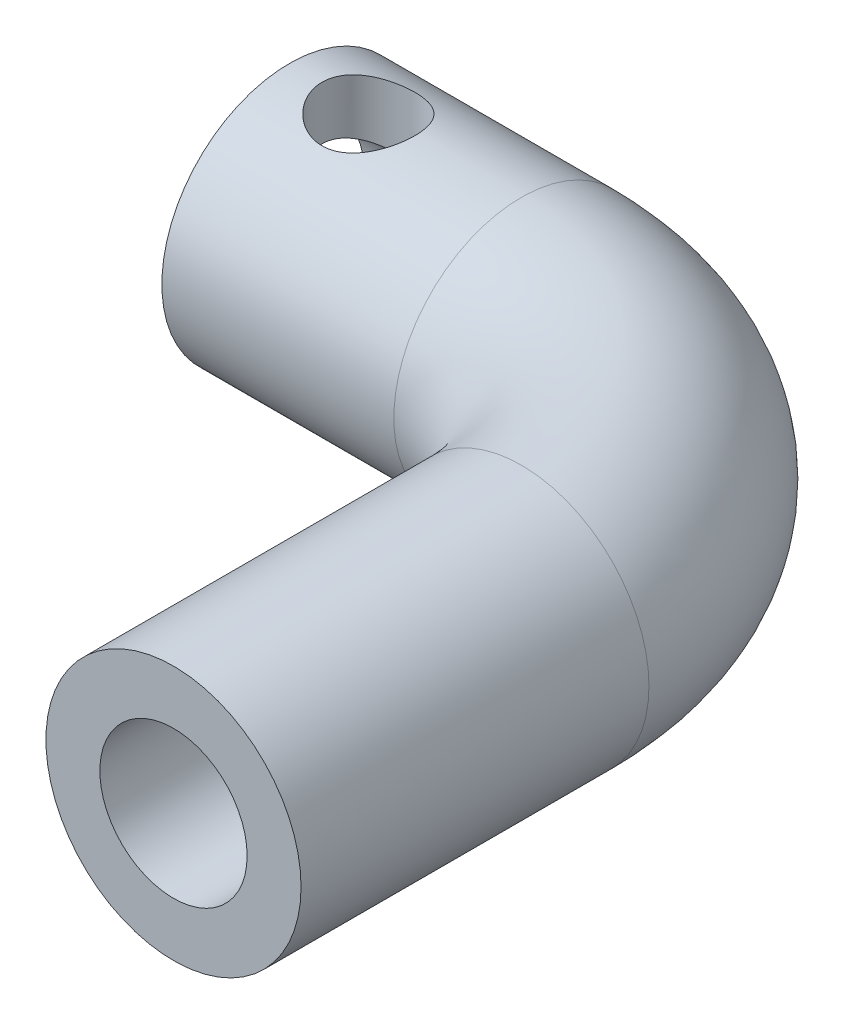
SolidWorks part; units mm, degrees
ref_plane "Front Plane" through (0, 0, 0) normal (0, 0, 1) x (1, 0, 0)
ref_plane "Top Plane" through (0, 0, 0) normal (0, 1, 0) x (1, 0, 0)
ref_plane "Right Plane" through (0, 0, 0) normal (1, 0, 0) x (0, 0, -1)
sketch "PROFILE" plane through (0, 0, 0) normal (0, 1, 0) x (1, 0, 0)
  line L0 (2.5, -10) -> (2.5, -25)
  line L1 (-7.5, 0) -> (-17.5, 0)
  arc A0 (2.5, -10) -> (-7.5, 0) centre (-7.5, -10) ccw
  dimension "D1" = 10
  dimension "D2" = 10
  dimension "D3" = 15
ref_plane "Plane1" through (0, 0, 25) normal (0, 0, 1) x (1, 0, 0)
sketch "Sketch4" plane through (0, 0, 25) normal (0, 0, 1) x (1, 0, 0)
  line L0 (2.5, 0) -> (-7.5, 0) construction
  circle A0 centre (2.5, 0) radius 5.5
  dimension "D1" = 11
sweep "Sweep2" add profiles "Sketch4" path "PROFILE"
sketch "Sketch6" plane through (0, 0, 25) normal (0, 0, 1) x (1, 0, 0)
  circle A0 centre (2.5, 0) radius 3.175
extrude "HOLE_SHAFT" cut sketch "Sketch6" against normal blind 10
sketch "Sketch7" plane through (-17.5, 0, 0) normal (-1, 0, 0) x (0, 0, 1)
  circle A0 centre (0, 0) radius 3.2
extrude "HOLE_POT" cut sketch "Sketch7" against normal blind 10
sketch "Sketch8" plane through (0, 0, 0) normal (0, 1, 0) x (1, 0, 0)
  line L0 (-7.5, 0) -> (-17.5, 0) construction
  circle A0 centre (-14.0963, 0) radius 2
  point P4 (-14.0963, 0)
extrude "Cut-Extrude3" cut sketch "Sketch8" along normal through all
ref_axis "Axis1" through (-18.775, 0, 0) along (1, 0, 0)
ref_plane "Plane2" through (0, 0, 0) normal (0, 1, 0) x (1, 0, 0)
sketch "Sketch11" plane through (-7.5, 0, 0) normal (-1, 0, 0) x (0, 0, 1)
  line L1 (-3.369, 0.5) -> (3.369, 0.5)
  line L2 (-3.369, 0.5) -> (-3.369, -0.5)
  line L3 (-3.369, -0.5) -> (3.369, -0.5)
  line L4 (3.369, 0.5) -> (3.369, -0.5)
  line L5 (-3.369, 0.5) -> (3.369, -0.5) construction
  line L6 (-3.369, -0.5) -> (3.369, 0.5) construction
  point P0 (0, 0)
  dimension "D1" = 1
extrude "Boss-Extrude2" add sketch "Sketch11" along normal blind 1
